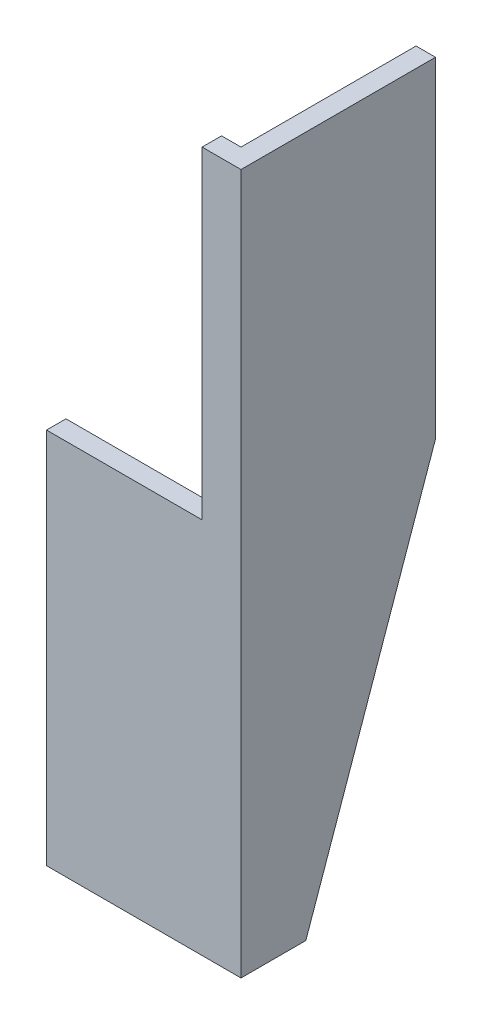
SolidWorks part; units mm, degrees
ref_plane "Alzado" through (0, 0, 0) normal (0, 0, 1) x (1, 0, 0)
ref_plane "Planta" through (0, 0, 0) normal (0, 1, 0) x (1, 0, 0)
ref_plane "Vista lateral" through (0, 0, 0) normal (1, 0, 0) x (0, 0, -1)
sketch "Croquis1" plane through (0, 0, 0) normal (0, 1, 0) x (1, 0, 0)
  line L0 (0, 0) -> (-50, 0)
  line L1 (0, 0) -> (0, 50)
  line L2 (-5, 5) -> (-5, 50)
  line L3 (-5, 5) -> (-50, 5)
  line L4 (-5, 50) -> (0, 50)
  line L5 (-50, 5) -> (-50, 0)
  dimension "D1" = 50
  dimension "D2" = 5
extrude "Saliente-Extruir1" add sketch "Croquis1" along normal blind 180
sketch "Croquis2" plane through (0, 0, 0) normal (1, 0, 0) x (0, 0, -1)
  line L0 (0, 95) -> (50, 95) construction
  line L1 (0, 180) -> (0, 0) construction
  line L2 (50, 180) -> (50, 0) construction
  line L3 (50, 180) -> (5, 180) construction
  line L4 (50, 95) -> (16.6667, 0)
  line L6 (16.6667, 0) -> (50, 0)
  line L7 (50, 0) -> (50, 95)
  dimension "D1" = 85
  dimension "D2" = 16.6667
extrude "Cortar-Extruir1" cut sketch "Croquis2" against normal up to surface (5 mm away) up to face at (-5, 90, -27.5)
sketch "Croquis3" plane through (0, 0, 0) normal (0, 0, 1) x (1, 0, 0)
  line L0 (0, 180) -> (0, 0) construction
  line L1 (-50, 180) -> (-10, 180)
  line L2 (-50, 180) -> (-50, 97)
  line L3 (-50, 97) -> (-10, 97)
  line L4 (-10, 180) -> (-10, 97)
  dimension "D1" = 83
  dimension "D2" = 10
extrude "Cortar-Extruir2" cut sketch "Croquis3" against normal up to surface (5 mm away) up to face at (-27.5, 90, -5)
